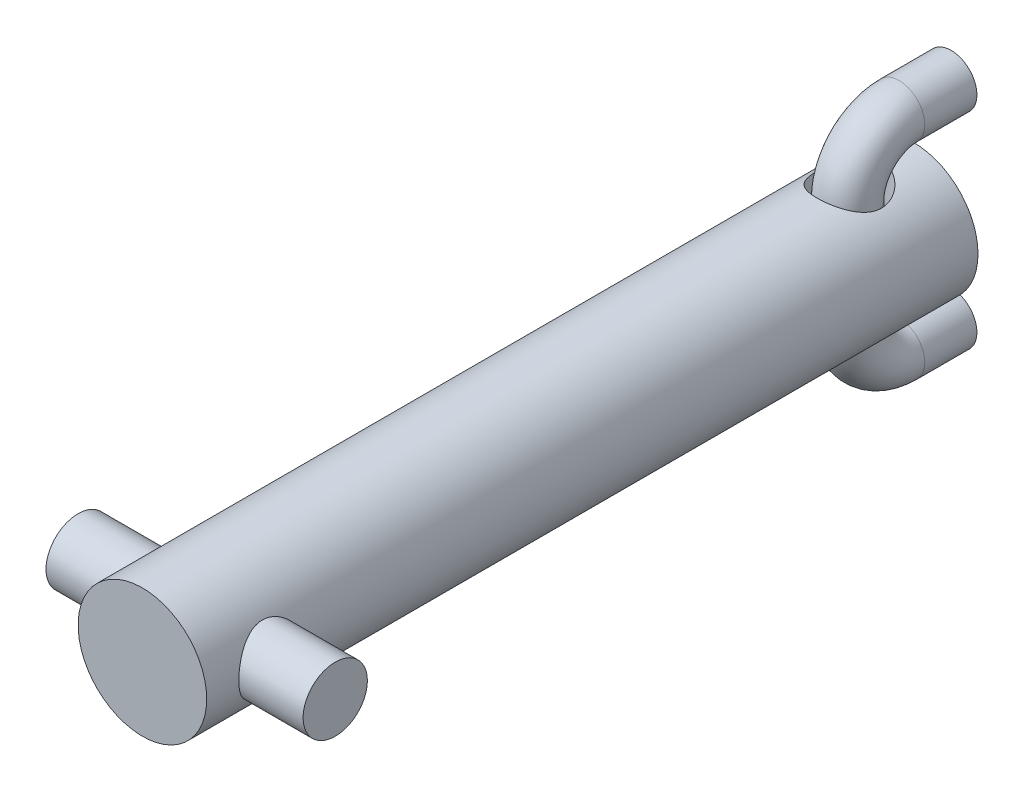
SolidWorks part; units mm, degrees
ref_plane "Front Plane" through (0, 0, 0) normal (0, 0, 1) x (1, 0, 0)
ref_plane "Top Plane" through (0, 0, 0) normal (0, 1, 0) x (1, 0, 0)
ref_plane "Right Plane" through (0, 0, 0) normal (1, 0, 0) x (0, 0, -1)
sketch "Sketch1" plane through (0, 0, 0) normal (0, 0, 1) x (1, 0, 0)
  circle A0 centre (0, 0) radius 3.175
  dimension "D1" = 6.35
extrude "Boss-Extrude1" add sketch "Sketch1" along normal blind 38.1
sketch "Sketch2" plane through (0, 0, 0) normal (0, 1, 0) x (1, 0, 0)
  circle A0 centre (0, -3.175) radius 1.5875
  dimension "D2" = 3.175
  dimension "D1" = 3.175
extrude "Cut-Extrude1" cut sketch "Sketch2" against normal mid plane 31.75
sketch "Sketch3" plane through (0, 0, 0) normal (1, 0, 0) x (0, 0, -1)
  line L0 (-38.1, 3.175) -> (-38.1, -3.175) construction
  circle A0 centre (-34.925, 0) radius 1.5875
  dimension "D1" = 3.175
  dimension "D2" = 3.175
  dimension "D3" = 3.175
extrude "Boss-Extrude2" add sketch "Sketch3" along normal mid plane 12.7
sketch "Sketch4" plane through (0, 0, 0) normal (1, 0, 0) x (0, 0, -1)
  line L0 (-3.263, -2.6975) -> (-3.263, 2.3825)
  line L1 (-0.723, 4.9225) -> (1.8504, 4.9225)
  line L2 (-0.723, -5.2375) -> (1.8504, -5.2375)
  arc A0 (-3.263, -2.6975) -> (-0.723, -5.2375) centre (-0.723, -2.6975) ccw
  arc A1 (-0.723, 4.9225) -> (-3.263, 2.3825) centre (-0.723, 2.3825) ccw
  point P3 (-3.263, -0.1575)
  point P7 (-3.263, -5.2375)
  point P10 (-3.263, 4.9225)
  dimension "D2" = 2.54
  dimension "D1" = 10.16
sweep "Sweep1" add path "Sketch4" circular profile diameter 2.54 parameters "D3"=2.54
